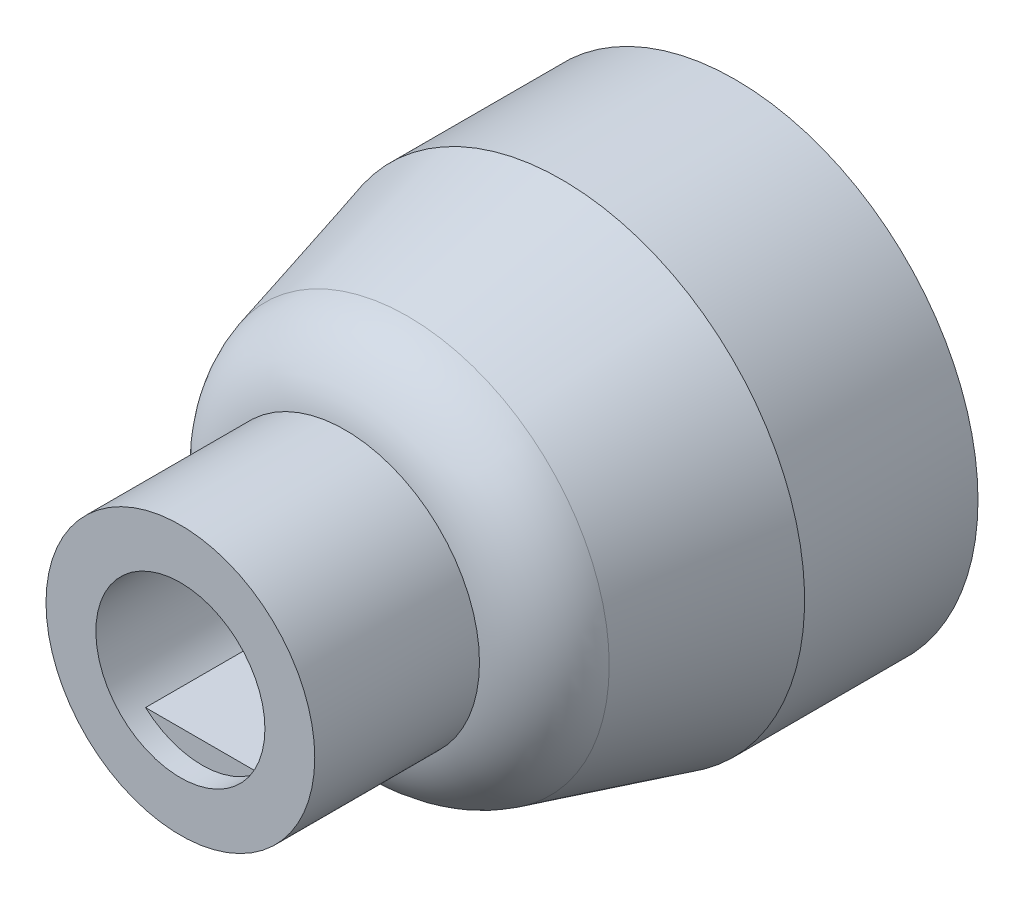
SolidWorks part; units mm, degrees
ref_plane "Front Plane" through (0, 0, 0) normal (0, 0, 1) x (1, 0, 0)
ref_plane "Top Plane" through (0, 0, 0) normal (0, 1, 0) x (1, 0, 0)
ref_plane "Right Plane" through (0, 0, 0) normal (1, 0, 0) x (0, 0, -1)
sketch "Sketch1" plane through (0, 0, 0) normal (0, 0, 1) x (1, 0, 0)
  circle A0 centre (0, 0) radius 5.6
  dimension "D1" = 11.2
extrude "Boss-Extrude1" add sketch "Sketch1" along normal blind 9
sketch "Sketch2" plane through (0, 0, 9) normal (0, 0, 1) x (1, 0, 0)
  line L0 (0, 1.45) -> (0, -1.45) construction
  line L1 (-1.3038, -1.45) -> (1.3038, -1.45)
  line L3 (-1.3038, 1.45) -> (1.3038, 1.45)
  circle A0 centre (0, 0) radius 3.1
  arc A1 (-1.3038, 1.45) -> (-1.3038, -1.45) centre (0, 0) ccw
  arc A2 (1.3038, -1.45) -> (1.3038, 1.45) centre (0, 0) ccw
  point P9 (0, -1.45)
  point P10 (0, 1.45)
  point P14 (0, 0)
  dimension "D1" = 6.2
  dimension "D2" = 3.9
  dimension "D3" = 2.9
extrude "Boss-Extrude2" add sketch "Sketch2" along normal blind 3.8
sketch "Sketch3" plane through (0, 0, 12.8) normal (0, 0, 1) x (1, 0, 0)
  circle A0 centre (0, 0) radius 1.95
  arc A1 (-1.3038, 1.45) -> (-1.3038, -1.45) centre (0, 0) ccw construction
  point P6 (-1.95, 0)
extrude "Cut-Extrude1" cut sketch "Sketch3" against normal blind 0.5
chamfer "Chamfer1" distance 5 angle 15 1 edges at (5.6, 0, 9) first distance on face at (5.6, 0, 9)
fillet "Fillet1" radius 2 1 edges at (4.2603, 0, 9)
